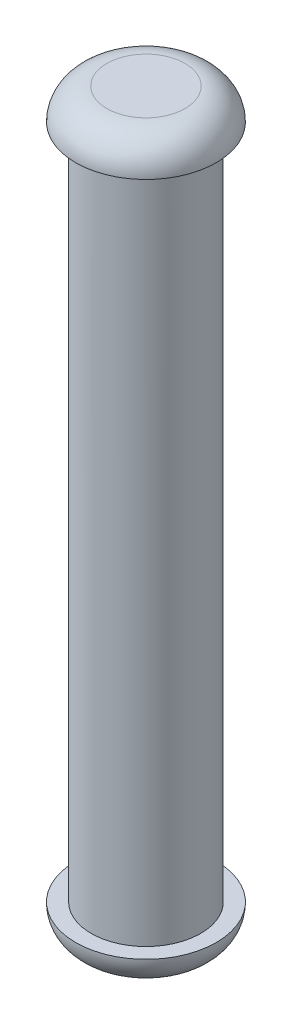
SolidWorks part; units mm, degrees
material "AISI 304"
ref_plane "Front Plane" through (0, 0, 0) normal (0, 0, 1) x (1, 0, 0)
ref_plane "Top Plane" through (0, 0, 0) normal (0, 1, 0) x (1, 0, 0)
ref_plane "Right Plane" through (0, 0, 0) normal (1, 0, 0) x (0, 0, -1)
sketch "Sketch1" plane through (0, 0, 0) normal (0, 1, 0) x (1, 0, 0)
  circle A0 centre (0, 0) radius 1.75
  dimension "D1" = 3.5
extrude "Boss-Extrude1" add sketch "Sketch1" along normal mid plane 22.6
sketch "Sketch2" plane through (0, 11.3, 0) normal (0, 1, 0) x (1, 0, 0)
  circle A0 centre (0, 0) radius 2.25
  dimension "D1" = 4.5
extrude "Boss-Extrude2" add sketch "Sketch2" along normal mid plane 1
mirror "Mirror1" about plane through (0, 0, 0) normal (0, 1, 0) of "Boss-Extrude2"
fillet "Fillet2" radius 1 2 edges at (0, -11.8, 2.25) (0, 11.8, 2.25)
